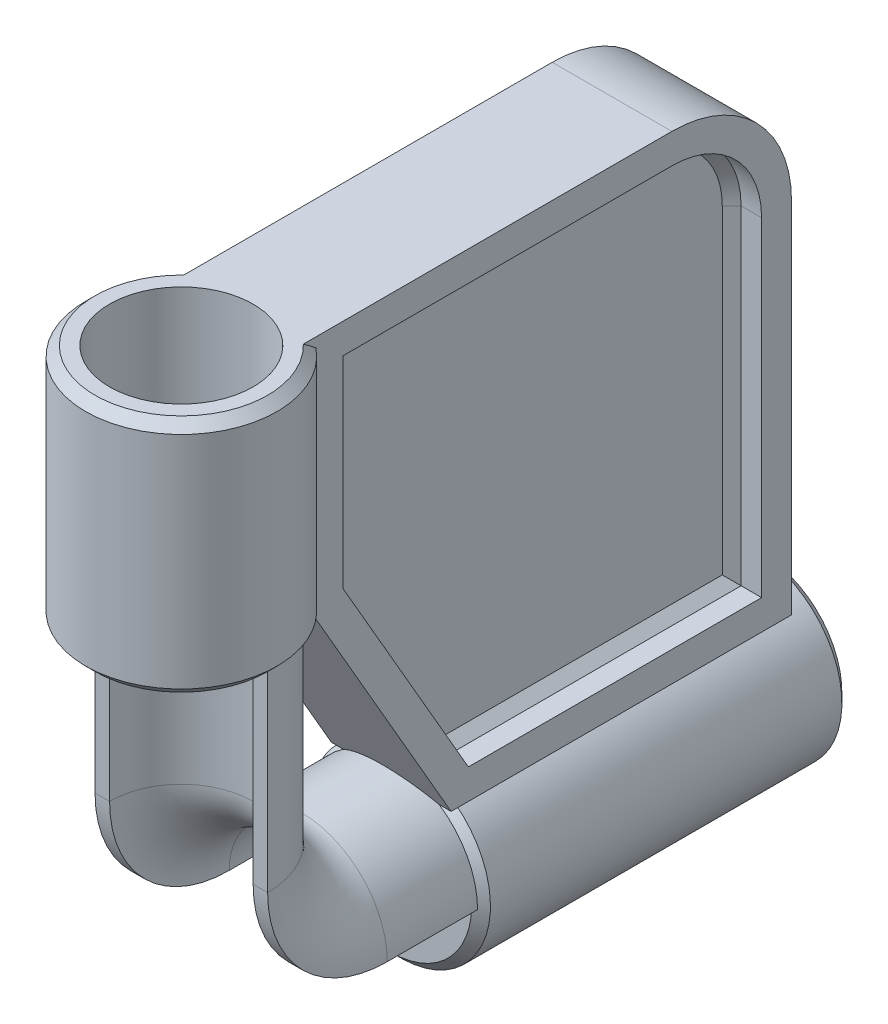
SolidWorks part; units mm, degrees
ref_plane "Front Plane" through (0, 0, 0) normal (1, 0, 0) x (0, 1, 0)
ref_plane "Top Plane" through (0, 0, 0) normal (0, 0, 1) x (0, 1, 0)
ref_plane "Right Plane" through (0, 0, 0) normal (0, 1, 0) x (-1, 0, 0)
sketch "Sketch1" plane through (0, 0, 0) normal (1, 0, 0) x (0, 1, 0)
  line L0 (-25.4, 10.7353) -> (0, 25.4)
  line L1 (-25.4, -25.4) -> (25.4, -25.4)
  line L2 (-25.4, -25.4) -> (-25.4, 10.7353)
  line L3 (0, 25.4) -> (25.4, 25.4)
  line L4 (25.4, -25.4) -> (25.4, 25.4)
  line L5 (0, -55) -> (0, 55) construction
  line L6 (55, 0) -> (-55, 0) construction
  point P0 (0, 0)
  point P10 (25.4, 0)
  dimension "D1" = 50.8
  dimension "D2" = 50.8
  dimension "D3" = 30
  dimension "D4" = 25.4
extrude "Boss-Extrude1" add sketch "Sketch1" along normal mid plane 12.7
fillet "Fillet1" radius 12.7 1 edges at (0, 25.4, -25.4)
sketch "Sketch3" plane through (6.35, 0, 0) normal (1, 0, 0) x (0, 1, 0)
  line L10 (-22.225, -22.225) -> (12.7, -22.225)
  line L11 (22.225, -12.7) -> (22.225, 22.225)
  line L12 (22.225, 22.225) -> (0.8507, 22.225)
  line L13 (0.8507, 22.225) -> (-22.225, 8.9022)
  line L14 (-22.225, 8.9022) -> (-22.225, -22.225)
  line L15 (-22.225, -22.225) -> (12.7, -22.225)
  line L16 (22.225, -12.7) -> (22.225, 22.225)
  line L17 (22.225, 22.225) -> (0.8507, 22.225)
  line L18 (0.8507, 22.225) -> (-22.225, 8.9022)
  line L19 (-22.225, 8.9022) -> (-22.225, -22.225)
  arc A2 (12.7, -22.225) -> (22.225, -12.7) centre (12.7, -12.7) ccw
  arc A3 (12.7, -22.225) -> (22.225, -12.7) centre (12.7, -12.7) ccw
  dimension "D1" = 3.175
extrude "Cut-Extrude2" cut sketch "Sketch3" against normal blind 3.175
mirror "Mirror1" about plane through (0, 0, 0) normal (1, 0, 0) of "Cut-Extrude2"
sketch "Sketch4" plane through (0, 0, -25.4) normal (0, 0, -1) x (1, 0, 0)
  line L0 (0, -27.94) -> (0, 27.94) construction
  line L1 (6.35, -25.4) -> (-6.35, -25.4) construction
  circle A0 centre (0, 33.02) radius 9.525
  circle A1 centre (0, 33.02) radius 6.35
  dimension "D1" = 19.05
  dimension "D2" = 12.7
  dimension "D3" = 58.42
extrude "Boss-Extrude2" add sketch "Sketch4" against normal up to vertex (36.1353 mm away) and the other way blind 3.175 up to point (6.35, -25.4, 10.7353)
sketch "Sketch5" plane through (0, 25.4, 0) normal (0, 1, 0) x (-1, 0, 0)
  line L0 (0, 29.6863) -> (0, -29.6863) construction
  line L1 (-5.715, -25.4) -> (5.715, -25.4) construction
  circle A0 centre (0, 33.02) radius 10.16
  circle A1 centre (0, 33.02) radius 7.62
  dimension "D1" = 20.32
  dimension "D2" = 15.24
  dimension "D3" = 58.42
extrude "Boss-Extrude3" add sketch "Sketch5" against normal up to surface (25.4 mm away) up to plane "Right Plane"
chamfer "Chamfer2" distance 1 angle 45 4 edges at (0, 0, 43.18) (0, -42.545, 10.7353) (0, -23.495, -28.575) (0, 25.4, 43.18)
sketch "Sketch6" plane through (0, 0, 0) normal (1, 0, 0) x (0, 1, 0)
  line L0 (-26.67, 10.7353) -> (-39.37, 10.7353) construction
  line L1 (-26.67, 10.7353) -> (-39.37, 10.7353) construction
  line L2 (0, 40.64) -> (0, 25.4) construction
  line L3 (0, 40.64) -> (0, 25.4) construction
  line L4 (-20.32, 33.02) -> (0, 33.02)
  line L5 (-33.02, 20.32) -> (-33.02, 10.7353)
  arc A0 (-33.02, 20.32) -> (-20.32, 33.02) centre (-20.32, 20.32) cw
  point P6 (-33.02, 10.7353)
  point P9 (0, 33.02)
  dimension "D1" = 12.7
sketch "Sketch7" plane through (0, 0, 0) normal (0, -1, 0) x (1, 0, 0)
  line L0 (-9.16, 33.02) -> (-7.62, 33.02)
  line L1 (7.62, 33.02) -> (9.16, 33.02)
  line L2 (0, 40.64) -> (0, 25.4) construction
  circle A0 centre (0, 33.02) radius 7.62 construction
  arc A4 (-7.62, 33.02) -> (7.62, 33.02) centre (0, 33.02) ccw
  arc A5 (-9.16, 33.02) -> (9.16, 33.02) centre (0, 33.02) ccw
  arc A6 (5.0834, 25.4) -> (-5.0834, 25.4) centre (0, 33.02) ccw construction
sweep "Sweep3" add profiles "Sketch7" path "Sketch6"
chamfer "Chamfer4" distance 1 angle 45 12 edges at (-3.175, -4.7625, -22.225) (-3.175, 19.4352, -19.4352) (-3.175, 22.225, 4.7625) (-3.175, 11.5379, 22.225) (-3.175, -10.6871, 15.5636) (-3.175, -22.225, -6.6614) (3.175, -10.6871, 15.5636) (3.175, 11.5379, 22.225) (3.175, 22.225, 4.7625) (3.175, 19.4352, -19.4352) (3.175, -4.7625, -22.225) (3.175, -22.225, -6.6614)
